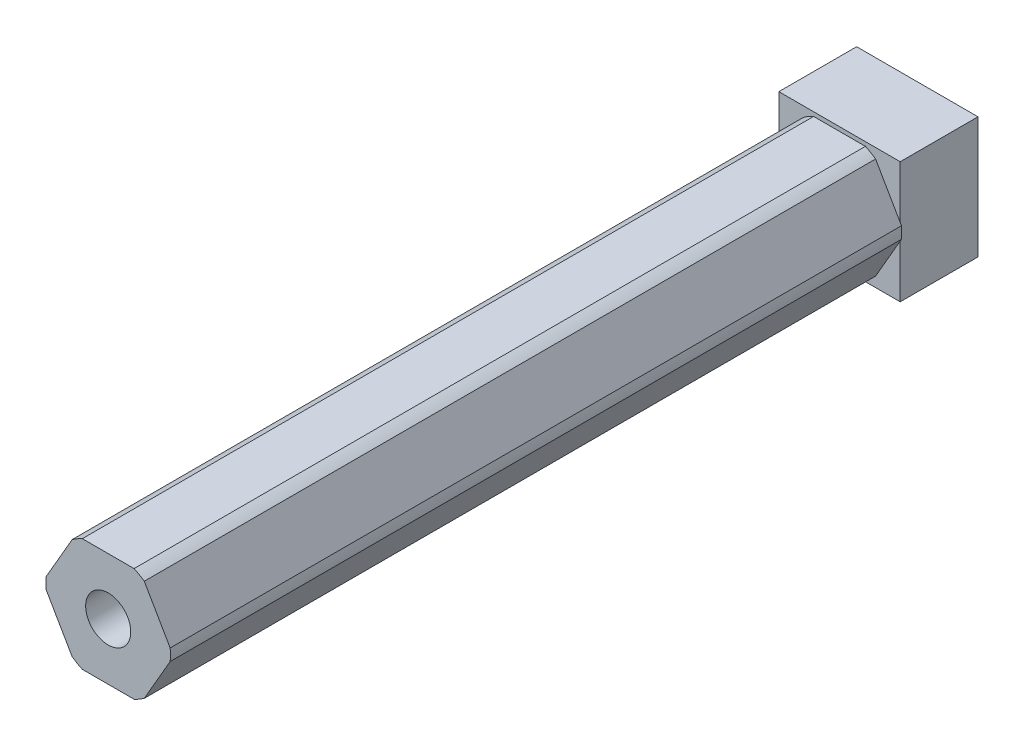
SolidWorks part; units mm, degrees
ref_plane "Спереди" through (0, 0, 0) normal (0, 0, 1) x (1, 0, 0)
ref_plane "Сверху" through (0, 0, 0) normal (0, 1, 0) x (1, 0, 0)
ref_plane "Справа" through (0, 0, 0) normal (1, 0, 0) x (0, 0, -1)
sketch "Эскиз1" plane through (0, 0, 0) normal (0, 0, 1) x (1, 0, 0)
  line L0 (1.6643, 3.6373) -> (-1.6643, 3.6373)
  line L1 (-2.3178, 3.26) -> (-3.9822, 0.3773)
  line L2 (-3.9822, -0.3773) -> (-2.3178, -3.26)
  line L3 (-1.6643, -3.6373) -> (1.6643, -3.6373)
  line L4 (2.3178, -3.26) -> (3.9822, -0.3773)
  line L5 (3.9822, 0.3773) -> (2.3178, 3.26)
  arc A0 (-1.6643, 3.6373) -> (-2.3178, 3.26) centre (0, 0) ccw
  arc A1 (2.3178, 3.26) -> (1.6643, 3.6373) centre (0, 0) ccw
  arc A2 (3.9822, -0.3773) -> (3.9822, 0.3773) centre (0, 0) ccw
  arc A3 (1.6643, -3.6373) -> (2.3178, -3.26) centre (0, 0) ccw
  arc A4 (-2.3178, -3.26) -> (-1.6643, -3.6373) centre (0, 0) ccw
  arc A5 (-3.9822, 0.3773) -> (-3.9822, -0.3773) centre (0, 0) ccw
  dimension "D1" = 8
  dimension "D2" = 3.3287
  dimension "D3" = 60
  dimension "D4" = 60
extrude "Бобышка-Вытянуть1" add sketch "Эскиз1" along normal blind 47
sketch "Эскиз2" plane through (0, 0, 0) normal (0, 0, -1) x (-1, 0, 0)
  line L1 (-3.9, -3.9) -> (3.9, -3.9)
  line L2 (-3.9, -3.9) -> (-3.9, 3.9)
  line L3 (-3.9, 3.9) -> (3.9, 3.9)
  line L4 (3.9, -3.9) -> (3.9, 3.9)
  line L5 (-3.9, -3.9) -> (3.9, 3.9) construction
  line L6 (-3.9, 3.9) -> (3.9, -3.9) construction
  point P0 (0, 0)
  dimension "D1" = 7.8
extrude "Бобышка-Вытянуть2" add sketch "Эскиз2" along normal blind 5
sketch "Эскиз3" plane through (0, 0, -5) normal (0, 0, -1) x (-1, 0, 0)
  circle A0 centre (0, 0) radius 1.45
  dimension "D1" = 2.9
extrude "Вырез-Вытянуть1" cut sketch "Эскиз3" against normal blind 12.5
sketch "Эскиз4" plane through (0, 0, -5) normal (0, 0, -1) x (-1, 0, 0)
  circle A0 centre (0, 0) radius 3
  dimension "D1" = 6
extrude "Вырез-Вытянуть2" cut sketch "Эскиз4" against normal blind 3
extrude "Вырез-Вытянуть3" cut sketch "Эскиз3<2>" along normal blind 9.5 from vertex starting at point (3.9822, 0.3773, 47)
sketch "Эскиз3<2>" plane through (0, 0, -5) normal (0, 0, -1) x (-1, 0, 0) same geometry as "Эскиз3"
